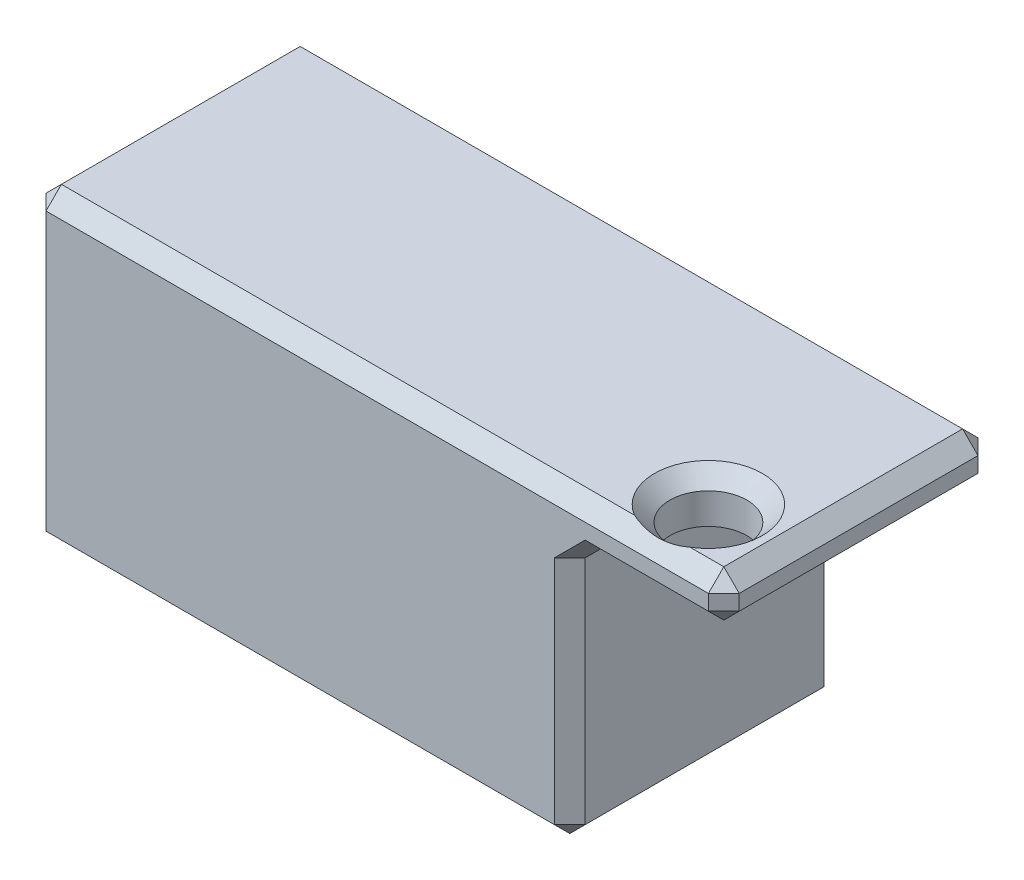
SolidWorks part; units mm, degrees
ref_plane "前视基准面" through (0, 0, 0) normal (0, 0, 1) x (1, 0, 0)
ref_plane "上视基准面" through (0, 0, 0) normal (0, 1, 0) x (1, 0, 0)
ref_plane "右视基准面" through (0, 0, 0) normal (1, 0, 0) x (0, 0, -1)
other "Configuration Table"
sketch "草图1" plane through (0, 0, 0) normal (0, 1, 0) x (1, 0, 0)
  line L1 (0, 0) -> (35, 0)
  line L2 (0, 0) -> (0, -8)
  line L3 (0, -8) -> (35, -8)
  line L4 (35, 0) -> (35, -8)
  dimension "D1" = 8
  dimension "D2" = 35
extrude "凸台-拉伸1" add sketch "草图1" along normal blind 20
sketch "草图2" plane through (0, 20, 0) normal (0, 1, 0) x (1, 0, 0)
  line L0 (35, 0) -> (0, 0) construction
  line L1 (35, 0) -> (45, 0)
  line L2 (35, 0) -> (35, -8)
  line L3 (35, -8) -> (45, -8)
  line L4 (45, 0) -> (45, -8)
  line L5 (35, -8) -> (35, 0) construction
  line L6 (0, -8) -> (35, -8) construction
  circle A0 centre (40, -4) radius 2.5
  dimension "D2" = 5
  dimension "D1" = 10
extrude "凸台-拉伸2" add sketch "草图2" against normal blind 3
sketch "草图3" plane through (0, 0, 0) normal (0, 0, -1) x (-1, 0, 0)
  line L14 (-35, 0) -> (0, 0)
  line L15 (-35, 0) -> (0, 0)
  line L16 (0, 0) -> (0, 20)
  line L17 (0, 0) -> (0, 20)
  line L18 (0, 20) -> (-45, 20)
  line L19 (0, 20) -> (-45, 20)
  line L20 (-45, 20) -> (-45, 17)
  line L21 (-45, 20) -> (-45, 17)
  line L22 (-45, 17) -> (-35, 17)
  line L23 (-45, 17) -> (-35, 17)
  line L32 (-35, 17) -> (-35, 0)
  line L33 (-35, 17) -> (-35, 0)
  dimension "D1" = 0
extrude "凸台-拉伸3" add sketch "草图3" along normal blind 9.5 and the other way blind 1
chamfer "倒角1" distance 1 angle 45 19 edges at (0, 20, -0.75) (0, 0, -0.75) (35, 0, -0.75) (35, 17, -0.75) (40, 17, -9.5) (35, 8.5, -9.5) (17.5, 0, -9.5) (0, 10, -9.5) (22.5, 20, -9.5) (45, 17, -0.75) (45, 18.5, -9.5) (45, 20, -0.75) (0, 10, 8) (22.5, 20, 8) (45, 18.5, 8) (40, 17, 8) (35, 8.5, 8) (17.5, 0, 8) (40, 20, 6.5)
